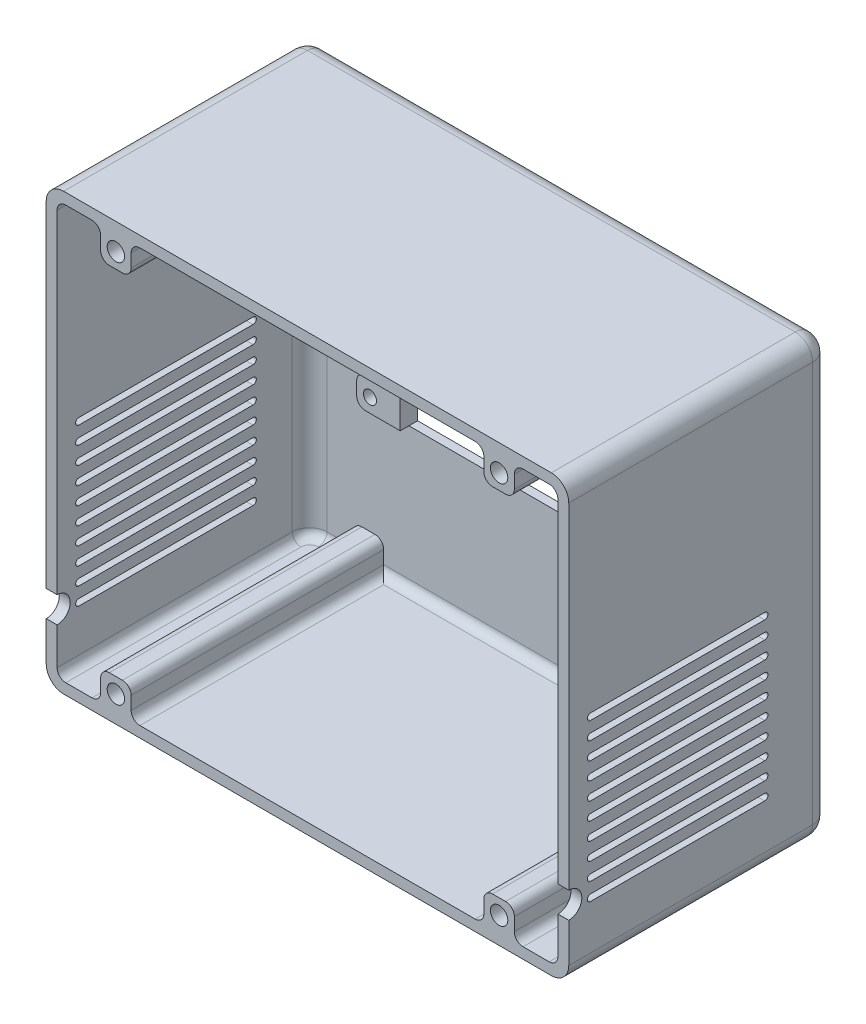
SolidWorks part; units mm, degrees
note: The reader was unsure of these and kept them because the rebuilt part matched: shared geometry of "Szkic1<8>", "Szkic1<9>", "Szkic1<10>".
ref_plane "Płaszczyzna przednia" through (0, 0, 0) normal (0, 0, 1) x (1, 0, 0)
ref_plane "Płaszczyzna górna" through (0, 0, 0) normal (0, 1, 0) x (1, 0, 0)
ref_plane "Płaszczyzna prawa" through (0, 0, 0) normal (1, 0, 0) x (0, 0, -1)
sketch "Szkic1" plane through (0, 0, 0) normal (0, 0, 1) x (1, 0, 0)
  line L1 (5.0238, 38.3681) -> (125.0238, 38.3681)
  line L2 (5.0238, 38.3681) -> (5.0238, -61.6319)
  line L3 (5.0238, -61.6319) -> (125.0238, -61.6319)
  line L4 (125.0238, 38.3681) -> (125.0238, -61.6319)
  line L5 (7.5238, 35.8681) -> (122.5238, 35.8681)
  line L6 (7.5238, 35.8681) -> (7.5238, -59.1319)
  line L7 (7.5238, -59.1319) -> (122.5238, -59.1319)
  line L8 (122.5238, 35.8681) -> (122.5238, -59.1319)
  line L9 (30.3238, 23.3681) -> (99.7238, 23.3681)
  line L10 (30.3238, 23.3681) -> (30.3238, -26.6319)
  line L11 (30.3238, -26.6319) -> (99.7238, -26.6319)
  line L12 (99.7238, 23.3681) -> (99.7238, -26.6319)
  line L13 (109.7238, 23.3681) -> (20.3238, 23.3681)
  line L14 (109.7238, 23.3681) -> (109.7238, -26.6319)
  line L15 (109.7238, -26.6319) -> (20.3238, -26.6319)
  line L16 (20.3238, 23.3681) -> (20.3238, -26.6319)
  line L17 (109.7238, 23.3681) -> (99.7238, 23.3681)
  line L18 (109.7238, 23.3681) -> (109.7238, 8.3681)
  line L19 (109.7238, 8.3681) -> (99.7238, 8.3681)
  line L20 (99.7238, 23.3681) -> (99.7238, 8.3681)
  line L21 (109.7238, -11.6319) -> (99.7238, -11.6319)
  line L22 (109.7238, -11.6319) -> (109.7238, -26.6319)
  line L23 (109.7238, -26.6319) -> (99.7238, -26.6319)
  line L24 (99.7238, -11.6319) -> (99.7238, -26.6319)
  line L25 (20.3238, -26.6319) -> (30.3238, -26.6319)
  line L26 (20.3238, -26.6319) -> (20.3238, -11.6319)
  line L27 (20.3238, -11.6319) -> (30.3238, -11.6319)
  line L28 (30.3238, -26.6319) -> (30.3238, -11.6319)
  line L29 (20.3238, 23.3681) -> (30.3238, 23.3681)
  line L30 (20.3238, 23.3681) -> (20.3238, 8.3681)
  line L31 (20.3238, 8.3681) -> (30.3238, 8.3681)
  line L32 (30.3238, 23.3681) -> (30.3238, 8.3681)
  line L45 (17.5238, -59.1319) -> (24.5238, -59.1319)
  line L46 (17.5238, -59.1319) -> (17.5238, -52.1319)
  line L47 (17.5238, -52.1319) -> (24.5238, -52.1319)
  line L48 (24.5238, -59.1319) -> (24.5238, -52.1319)
  line L53 (17.5238, 35.8681) -> (24.5238, 35.8681)
  line L54 (17.5238, 35.8681) -> (17.5238, 28.8681)
  line L55 (17.5238, 28.8681) -> (24.5238, 28.8681)
  line L56 (24.5238, 35.8681) -> (24.5238, 28.8681)
  line L57 (105.5238, 35.8681) -> (112.5238, 35.8681)
  line L58 (105.5238, 35.8681) -> (105.5238, 28.8681)
  line L59 (105.5238, 28.8681) -> (112.5238, 28.8681)
  line L60 (112.5238, 35.8681) -> (112.5238, 28.8681)
  line L61 (112.5238, -59.1319) -> (105.5238, -59.1319)
  line L62 (112.5238, -59.1319) -> (112.5238, -52.1319)
  line L63 (112.5238, -52.1319) -> (105.5238, -52.1319)
  line L64 (105.5238, -59.1319) -> (105.5238, -52.1319)
  circle A0 centre (23.5238, 20.1681) radius 1.5
  circle A3 centre (23.366, -23.4319) radius 1.5
  circle A4 centre (106.5238, -23.4319) radius 1.5
  circle A5 centre (106.366, 20.1681) radius 1.5
  dimension "D13" = 3.2
  dimension "D15" = 3.2
  dimension "D18" = 2.5
  dimension "D1" = 100
  dimension "D2" = 120
  dimension "D3" = 50
  dimension "D4" = 69.4
  dimension "D5" = 15
  dimension "D6" = 25.3
  dimension "D7" = 20
  dimension "D8" = 20
  dimension "D9" = 15
  dimension "D10" = 15
  dimension "D11" = 10
  dimension "D12" = 10
  dimension "D14" = 3.2
  dimension "D16" = 3.2
  dimension "D17" = 3.2
  dimension "D19" = 2.5
  dimension "D20" = 7
  dimension "D21" = 10
  dimension "D22" = 7
  dimension "D23" = 7
  dimension "D24" = 10
  dimension "D25" = 7
  dimension "D26" = 2.5
  dimension "D27" = 2.5
extrude "Dodanie-wyciągnięcie2" add sketch "Szkic1" along normal blind 4 contours L31 L16 L27 L10 | L21 L14 L19 L12 | L16 L31 L10 L13 | L27 L16 L15 L10 | L19 L14 L13 L12 | L14 L21 L12 L15
extrude "Dodanie-wyciągnięcie4" add sketch "Szkic1<8>" along normal blind 2 contours L8 L5 L6 L7 L16 L13 L9 L14 L15 L11
sketch "Szkic1<8>" plane through (0, 0, 0) normal (0, 0, 1) x (1, 0, 0) same geometry as "Szkic1"
extrude "Dodanie-wyciągnięcie5" add sketch "Szkic1<9>" along normal blind 60 contours L4 L1 L2 L3 L5 L8 L7 L6 | L54 L53 L56 L55 | L58 L57 L60 L59 | L62 L61 L64 L63 | L46 L45 L48 L47
sketch "Szkic1<9>" plane through (0, 0, 0) normal (0, 0, 1) x (1, 0, 0) same geometry as "Szkic1"
extrude "Dodanie-wyciągnięcie6" add sketch "Szkic1<10>" along normal blind 1 contours A5 | A0 | A3 | A4
sketch "Szkic1<10>" plane through (0, 0, 0) normal (0, 0, 1) x (1, 0, 0) same geometry as "Szkic1"
sketch "Szkic4" plane through (0, 0, 4) normal (0, 0, 1) x (1, 0, 0)
sketch "Szkic5" plane through (0, 0, 4) normal (0, 0, 1) x (1, 0, 0)
  line L0 (20.3238, 23.3681) -> (20.3238, -26.6319) construction
  line L1 (20.3238, 16.3681) -> (30.3238, 16.3681)
  line L2 (20.3238, 16.3681) -> (20.3238, -19.6319)
  line L3 (20.3238, -19.6319) -> (30.3238, -19.6319)
  line L4 (30.3238, 16.3681) -> (30.3238, -19.6319)
  line L5 (30.3238, 23.3681) -> (30.3238, -26.6319) construction
  line L7 (30.3238, 23.3681) -> (20.3238, 23.3681) construction
  line L8 (30.3238, -26.6319) -> (20.3238, -26.6319) construction
  line L9 (109.7238, 23.3681) -> (109.7238, -26.6319) construction
  line L10 (109.7238, 16.3681) -> (99.7238, 16.3681)
  line L11 (109.7238, 16.3681) -> (109.7238, -19.6319)
  line L12 (109.7238, -19.6319) -> (99.7238, -19.6319)
  line L13 (99.7238, 16.3681) -> (99.7238, -19.6319)
  line L14 (99.7238, 23.3681) -> (99.7238, -26.6319) construction
  line L15 (109.7238, 23.3681) -> (99.7238, 23.3681) construction
  line L16 (109.7238, -26.6319) -> (99.7238, -26.6319) construction
  dimension "D1" = 7
  dimension "D2" = 7
  dimension "D3" = 7
  dimension "D4" = 7
extrude "Wytnij-wyciągnięcie1" cut sketch "Szkic5" against normal blind 2
sketch "Szkic7" plane through (0, 0, 2) normal (0, 0, 1) x (1, 0, 0)
sketch "Szkic8" plane through (0, 0, 60) normal (0, 0, 1) x (1, 0, 0)
sketch "Szkic9" plane through (0, 0, 60) normal (0, 0, 1) x (1, 0, 0)
  line L0 (17.5238, 28.8681) -> (24.5238, 28.8681) construction
  line L1 (24.5238, 35.8681) -> (24.5238, 28.8681) construction
  line L2 (112.5238, 35.8681) -> (112.5238, 28.8681) construction
  line L3 (105.5238, 28.8681) -> (112.5238, 28.8681) construction
  line L4 (112.5238, -52.1319) -> (105.5238, -52.1319) construction
  line L5 (105.5238, -59.1319) -> (105.5238, -52.1319) construction
  line L6 (24.5238, -59.1319) -> (24.5238, -52.1319) construction
  line L7 (17.5238, -52.1319) -> (24.5238, -52.1319) construction
  line L8 (5.0238, 38.3681) -> (125.0238, 38.3681) construction
  circle A0 centre (21.0238, 32.3681) radius 2
  circle A1 centre (109.0238, 32.3681) radius 2
  circle A2 centre (21.0238, -55.6319) radius 2
  circle A3 centre (109.0238, -55.6319) radius 2
  point P10 (0, 0)
  point P11 (0, 0)
  dimension "D1" = 3.5
  dimension "D2" = 3.5
  dimension "D3" = 3.5
  dimension "D4" = 3.5
  dimension "D5" = 3.5
  dimension "D6" = 3.5
  dimension "D7" = 3.5
  dimension "D8" = 3.5
extrude "Wytnij-wyciągnięcie2" cut sketch "Szkic9" against normal blind 32 contours A0 | A1 | A3 | A2
sketch "Szkic11" plane through (5.0238, 0, 0) normal (-1, 0, 0) x (0, 0, 1)
  line L0 (0, 38.3681) -> (0, -61.6319) construction
  line L1 (15, -45.8819) -> (55, -45.8819)
  line L3 (15, -47.3819) -> (55, -47.3819)
  line L5 (60, 38.3681) -> (60, -61.6319) construction
  line L6 (60, -61.6319) -> (0, -61.6319) construction
  line L7 (15, -41.8819) -> (55, -41.8819)
  line L8 (15, -43.3819) -> (55, -43.3819)
  line L9 (15, -37.8819) -> (55, -37.8819)
  line L10 (15, -39.3819) -> (55, -39.3819)
  line L11 (15, -33.8819) -> (55, -33.8819)
  line L12 (15, -35.3819) -> (55, -35.3819)
  line L13 (15, -29.8819) -> (55, -29.8819)
  line L14 (15, -31.3819) -> (55, -31.3819)
  line L15 (15, -25.8819) -> (55, -25.8819)
  line L16 (15, -27.3819) -> (55, -27.3819)
  line L17 (15, -21.8819) -> (55, -21.8819)
  line L18 (15, -23.3819) -> (55, -23.3819)
  line L19 (15, -17.8819) -> (55, -17.8819)
  line L20 (15, -19.3819) -> (55, -19.3819)
  line L21 (15, -13.8819) -> (55, -13.8819)
  line L22 (15, -15.3819) -> (55, -15.3819)
  line L23 (15, -9.8819) -> (55, -9.8819)
  line L24 (15, -11.3819) -> (55, -11.3819)
  arc A2 (55, -45.8819) -> (55, -47.3819) centre (55, -46.6319) cw
  arc A3 (15, -45.8819) -> (15, -47.3819) centre (15, -46.6319) ccw
  arc A4 (55, -41.8819) -> (55, -43.3819) centre (55, -42.6319) cw
  arc A5 (15, -41.8819) -> (15, -43.3819) centre (15, -42.6319) ccw
  arc A6 (55, -37.8819) -> (55, -39.3819) centre (55, -38.6319) cw
  arc A7 (15, -37.8819) -> (15, -39.3819) centre (15, -38.6319) ccw
  arc A8 (55, -33.8819) -> (55, -35.3819) centre (55, -34.6319) cw
  arc A9 (15, -33.8819) -> (15, -35.3819) centre (15, -34.6319) ccw
  arc A10 (55, -29.8819) -> (55, -31.3819) centre (55, -30.6319) cw
  arc A11 (15, -29.8819) -> (15, -31.3819) centre (15, -30.6319) ccw
  arc A12 (55, -25.8819) -> (55, -27.3819) centre (55, -26.6319) cw
  arc A13 (15, -25.8819) -> (15, -27.3819) centre (15, -26.6319) ccw
  arc A14 (55, -21.8819) -> (55, -23.3819) centre (55, -22.6319) cw
  arc A15 (15, -21.8819) -> (15, -23.3819) centre (15, -22.6319) ccw
  arc A16 (55, -17.8819) -> (55, -19.3819) centre (55, -18.6319) cw
  arc A17 (15, -17.8819) -> (15, -19.3819) centre (15, -18.6319) ccw
  arc A18 (55, -13.8819) -> (55, -15.3819) centre (55, -14.6319) cw
  arc A19 (15, -13.8819) -> (15, -15.3819) centre (15, -14.6319) ccw
  arc A20 (55, -9.8819) -> (55, -11.3819) centre (55, -10.6319) cw
  arc A21 (15, -9.8819) -> (15, -11.3819) centre (15, -10.6319) ccw
  dimension "D1" = 1.5
  dimension "D2" = 15
  dimension "D3" = 5
  dimension "D4" = 15
  dimension "D5" = 10
extrude "Wytnij-wyciągnięcie3" cut sketch "Szkic11" against normal through all both and the other way through all
sketch "Szkic13" plane through (5.0238, 0, 0) normal (-1, 0, 0) x (0, 0, 1)
  line L0 (60, 38.3681) -> (60, -61.6319) construction
  line L1 (60, -61.6319) -> (0, -61.6319) construction
  circle A0 centre (60, -45.6319) radius 3
  dimension "D1" = 16
extrude "Wytnij-wyciągnięcie4" cut sketch "Szkic13" against normal through all
fillet "Zaokrąglenie2" radius 4 9 edges at (65.0238, -61.6319, 0) (125.0238, -11.6319, 0) (65.0238, 38.3681, 0) (7.5238, -11.6319, 2) (5.0238, -61.6319, 30) (125.0238, -61.6319, 30) (125.0238, 38.3681, 30) (5.0238, 38.3681, 30) (5.0238, -11.6319, 0)
fillet "Zaokrąglenie3" radius 2 37 edges at (24.5238, 35.8681, 31) (112.5238, 35.8681, 31) (122.5238, 35.8681, 31) (122.5238, -59.1319, 31) (112.5238, -59.1319, 31) (105.5238, -59.1319, 31) (24.5238, -59.1319, 31) (17.5238, -59.1319, 31) (7.5238, -59.1319, 33) (7.5238, 35.8681, 33) (17.5238, -52.1319, 31) (24.5238, -52.1319, 31) (105.5238, -52.1319, 31) (112.5238, -52.1319, 31) (112.5238, 28.8681, 31) (105.5238, 35.8681, 31) (105.5238, 28.8681, 31) (24.5238, 28.8681, 31) (17.5238, 35.8681, 31) (17.5238, 28.8681, 31) (20.3238, -26.6319, 3) (20.3238, 23.3681, 3) (20.3238, -19.6319, 3) (20.3238, 16.3681, 3) (109.7238, 16.3681, 3) (109.7238, -19.6319, 3) (122.5238, -11.6319, 2) (117.5238, 35.8681, 2) (65.0238, 35.8681, 2) (65.0238, -59.1319, 2) (117.5238, -59.1319, 2) (14.5238, 35.8681, 2) (14.5238, -59.1319, 2) (8.6954, -59.1319, 3.1716) (8.6954, 35.8681, 3.1716) (109.7238, -26.6319, 3) (109.7238, 23.3681, 3)
